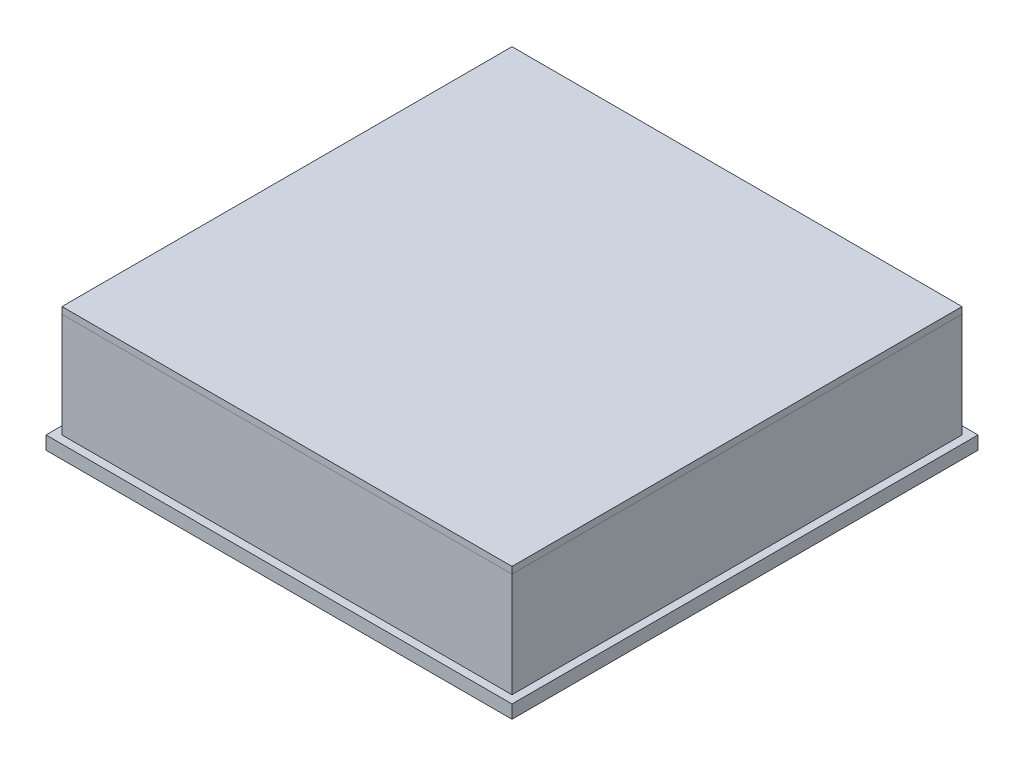
SolidWorks part; units mm, degrees
ref_plane "Front Plane" through (0, 0, 0) normal (0, 0, 1) x (1, 0, 0)
ref_plane "Top Plane" through (0, 0, 0) normal (0, 1, 0) x (1, 0, 0)
ref_plane "Right Plane" through (0, 0, 0) normal (1, 0, 0) x (0, 0, -1)
sketch "Sketch2" plane through (0, 0, 0) normal (0, 1, 0) x (1, 0, 0)
  line L0 (-4304.792, -4304.792) -> (-4304.792, 4304.792)
  line L1 (3999.992, -3999.992) -> (-3999.992, -3999.992)
  line L2 (3999.992, -3999.992) -> (3999.992, 3999.992)
  line L3 (3999.992, 3999.992) -> (-3999.992, 3999.992)
  line L4 (-3999.992, -3999.992) -> (-3999.992, 3999.992)
  line L5 (3999.992, -3999.992) -> (-3999.992, 3999.992) construction
  line L6 (3999.992, 3999.992) -> (-3999.992, -3999.992) construction
  line L7 (4304.792, 4304.792) -> (-4304.792, 4304.792)
  line L8 (4304.792, -4304.792) -> (4304.792, 4304.792)
  line L9 (4304.792, -4304.792) -> (-4304.792, -4304.792)
  point P0 (0, 0)
  dimension "D1" = 7999.984
  dimension "D2" = 7999.984
  dimension "D3" = 304.8
extrude "Boss-Extrude1" add sketch "Sketch2" along normal blind 1999.996
sketch "Sketch3" plane through (0, 0, 0) normal (0, -1, 0) x (1, 0, 0)
  line L0 (-4304.792, -4304.792) -> (-4304.792, 4304.792) construction
  line L1 (-4304.792, -4304.792) -> (-4304.792, 4304.792)
  line L2 (4304.792, -4304.792) -> (-4304.792, -4304.792) construction
  line L3 (4304.792, 4304.792) -> (4304.792, -4304.792) construction
  line L4 (-4304.792, 4304.792) -> (4304.792, 4304.792) construction
  line L5 (4304.792, -4304.792) -> (-4304.792, -4304.792)
  line L6 (4304.792, 4304.792) -> (4304.792, -4304.792)
  line L7 (-4304.792, 4304.792) -> (4304.792, 4304.792)
extrude "Boss-Extrude2" add sketch "Sketch3" along normal blind 152.4
sketch "Sketch6" plane through (0, 0, 0) normal (0, 1, 0) x (1, 0, 0)
  line L0 (0, 0) -> (-3999.992, 3999.992) construction
  line L6 (-3999.992, 1656.8509) -> (-1656.8509, 1656.8509) construction
  line L7 (-3999.992, 3999.992) -> (-3999.992, -3999.992) construction
  line L19 (-1656.8509, 1656.8509) -> (-1656.8509, 3999.992) construction
  line L20 (3999.992, 3999.992) -> (-3999.992, 3999.992) construction
  line L22 (-1656.8509, 1656.8509) -> (0, 0) construction
  line L24 (1809.2509, 1504.4509) -> (1809.2509, 1809.2509)
  line L25 (-1504.4509, 1809.2509) -> (-1809.2509, 1809.2509)
  line L29 (-1504.4509, 1809.2509) -> (-1504.4509, 1504.4509)
  line L30 (-1504.4509, 1504.4509) -> (-1809.2509, 1504.4509)
  line L31 (-1809.2509, 1809.2509) -> (-1809.2509, 1504.4509)
  line L32 (-1504.4509, 1809.2509) -> (-1809.2509, 1504.4509) construction
  line L33 (-1504.4509, 1504.4509) -> (-1809.2509, 1809.2509) construction
  line L34 (1809.2509, 1809.2509) -> (1504.4509, 1809.2509)
  line L35 (1504.4509, 1504.4509) -> (1504.4509, 1809.2509)
  line L36 (1809.2509, 1504.4509) -> (1504.4509, 1504.4509)
  line L37 (1504.4509, -1809.2509) -> (1809.2509, -1809.2509)
  line L38 (1809.2509, -1809.2509) -> (1809.2509, -1504.4509)
  line L39 (1504.4509, -1504.4509) -> (1809.2509, -1504.4509)
  line L40 (1504.4509, -1809.2509) -> (1504.4509, -1504.4509)
  line L41 (-1809.2509, -1504.4509) -> (-1809.2509, -1809.2509)
  line L42 (-1809.2509, -1809.2509) -> (-1504.4509, -1809.2509)
  line L43 (-1504.4509, -1504.4509) -> (-1504.4509, -1809.2509)
  line L44 (-1809.2509, -1504.4509) -> (-1504.4509, -1504.4509)
  point P30 (0, 0)
  dimension "D1" = 304.8
extrude "Boss-Extrude5" add sketch "Sketch6" along normal up to surface (1999.996 mm away) contours L25 L31 L30 L29 | L36 L24 L34 L35 | L40 L37 L38 L39 | L44 L41 L42 L43 region at (1656.8509, 0, -1656.8509) region at (-1656.8509, 0, -1656.8509) region at (1656.8509, 0, 1656.8509) region at (-1656.8509, 0, 1656.8509) up to face at (0, 1999.996, 0)
sketch "Sketch7" plane through (0, 1999.996, 0) normal (0, 1, 0) x (1, 0, 0)
  line L1 (4304.792, -4304.792) -> (-4304.792, -4304.792)
  line L2 (4304.792, -4304.792) -> (4304.792, 4304.792)
  line L3 (4304.792, 4304.792) -> (-4304.792, 4304.792)
  line L4 (-4304.792, -4304.792) -> (-4304.792, 4304.792)
  line L5 (4304.792, -4304.792) -> (-4304.792, 4304.792) construction
  line L6 (4304.792, 4304.792) -> (-4304.792, -4304.792) construction
  point P0 (0, 0)
extrude "Boss-Extrude6" add sketch "Sketch7" along normal blind 127 separate body
sketch "Sketch4" plane through (0, -152.4, 0) normal (0, -1, 0) x (1, 0, 0)
  line L30 (-4457.192, 4457.192) -> (-4457.192, -4457.192)
  line L31 (-4457.192, -4457.192) -> (4457.192, -4457.192)
  line L32 (4457.192, -4457.192) -> (4457.192, 4457.192)
  line L33 (4457.192, 4457.192) -> (-4457.192, 4457.192)
  line L34 (-4457.192, 4457.192) -> (-4457.192, -4457.192)
  line L35 (-4457.192, -4457.192) -> (4457.192, -4457.192)
  line L36 (4457.192, -4457.192) -> (4457.192, 4457.192)
  line L37 (4457.192, 4457.192) -> (-4457.192, 4457.192)
  line L43 (3847.592, 3847.592) -> (-3847.592, 3847.592)
  line L44 (-3847.592, 3847.592) -> (-3847.592, -3847.592)
  line L45 (-3847.592, -3847.592) -> (3847.592, -3847.592)
  line L46 (3847.592, -3847.592) -> (3847.592, 3847.592)
  line L47 (3847.592, 3847.592) -> (-3847.592, 3847.592)
  line L48 (-3847.592, 3847.592) -> (-3847.592, -3847.592)
  line L49 (-3847.592, -3847.592) -> (3847.592, -3847.592)
  line L50 (3847.592, -3847.592) -> (3847.592, 3847.592)
  dimension "D1" = 152.4
  dimension "D2" = 152.4
extrude "Boss-Extrude3" [suppressed] add sketch "Sketch4" along normal blind 304.8
sketch "Sketch8" plane through (0, 0, -1504.4509) normal (0, 0, 1) x (1, 0, 0)
  line L0 (-3999.992, 1999.996) -> (-3999.992, 0) construction
  line L1 (3999.992, 1999.996) -> (-3999.992, 1999.996)
  line L2 (3999.992, 1999.996) -> (3999.992, 1753.1524)
  line L3 (3999.992, 1753.1524) -> (-3999.992, 1753.1524)
  line L4 (-3999.992, 1999.996) -> (-3999.992, 1753.1524)
  line L5 (3999.992, 1999.996) -> (-3999.992, 1753.1524) construction
  line L6 (3999.992, 1753.1524) -> (-3999.992, 1999.996) construction
  line L7 (3999.992, 1999.996) -> (-3999.992, 1999.996) construction
  line L8 (3999.992, 1999.996) -> (-3999.992, 1999.996)
  point P0 (0, 1876.5742)
ref_axis "Axis1" through (0, 0, 0) along (0, 1, 0)
sketch "Right Plane Rebar" [suppressed] plane through (0, 0, 0) normal (1, 0, 0) x (0, 0, -1)
  line L0 (4234.942, 2063.496) -> (4234.942, -393.7)
  line L1 (-4457.192, -457.2) -> (4457.192, -457.2) construction
  line L2 (4069.842, 2044.446) -> (4069.842, 50.8)
  line L3 (4222.242, 1314.196) -> (4222.242, 1923.796)
  line L4 (-4304.792, 1999.996) -> (-4304.792, -152.4)
  line L5 (-4304.792, -152.4) -> (4304.792, -152.4)
  line L6 (4304.792, -152.4) -> (4304.792, 1999.996)
  line L7 (4304.792, 1999.996) -> (-4304.792, 1999.996)
  line L8 (-4304.792, 1999.996) -> (-4304.792, -152.4)
  line L10 (4304.792, -152.4) -> (4304.792, 1999.996)
  line L12 (4095.242, 2050.796) -> (3485.642, 2050.796)
  line L13 (4095.242, 2063.496) -> (-4095.242, 2063.496)
  line L14 (0, 1421.3078) -> (0, -1421.3078) construction
  line L15 (3955.542, -88.9) -> (-3955.542, -88.9)
  line L16 (3999.992, 1999.996) -> (-3999.992, 1999.996)
  line L17 (3999.992, 1999.996) -> (-3999.992, 1999.996)
  line L18 (-4304.792, 2126.996) -> (4304.792, 2126.996) construction
  line L19 (3999.992, 0) -> (3999.992, 1999.996)
  line L20 (-3999.992, 0) -> (3999.992, 0)
  line L21 (-3999.992, 1999.996) -> (-3999.992, 0)
  line L27 (3999.992, 0) -> (3999.992, 1999.996)
  line L28 (-3999.992, 0) -> (3999.992, 0)
  line L29 (-3999.992, 1999.996) -> (-3999.992, 0)
  line L32 (4082.542, 660.4) -> (4082.542, 50.8)
  line L33 (3955.542, -76.2) -> (3345.942, -76.2)
  line L37 (-4304.792, -152.4) -> (4304.792, -152.4)
  line L38 (4304.792, 1999.996) -> (-4304.792, 1999.996)
  arc A0 (4222.242, 1923.796) -> (4095.242, 2050.796) centre (4095.242, 1923.796) ccw
  arc A1 (3955.542, -76.2) -> (4082.542, 50.8) centre (3955.542, 50.8) ccw
  point P23 (4222.242, 2050.796)
  point P30 (0, 2063.496)
  point P41 (0, -88.9)
  dimension "D12" = 127
  dimension "D19" = 127
  dimension "D5" = 69.85
  dimension "Vertical Rebar Outer" = 2457.196
  dimension "D4" = 63.5
  dimension "D8" = 69.85
  dimension "D11" = 12.7
  dimension "D10" = 6.35
  dimension "D13" = 24000
  dimension "D14" = 609.6
  dimension "D15" = 12.7
  dimension "D17" = 12.7
  dimension "D18" = 12.7
  dimension "D7" = 609.6
  dimension "D20" = 609.6
  dimension "Vertical Rebar Inner" = 1993.646
  dimension "Lid Rebar Length" = 8190.484
  dimension "Base Rebar Length" = 7911.084
  dimension "D3" = 63.5
  dimension "D6" = 63.5
  dimension "D1" = 0
  dimension "D2" = 0
sketch "Front Plane Rebar" [suppressed] plane through (0, 0, 0) normal (0, 0, 1) x (1, 0, 0)
  line L0 (4247.642, 2063.496) -> (4247.642, -393.7)
  line L1 (3999.992, 1999.996) -> (3999.992, 0) construction
  line L2 (4057.142, 2031.746) -> (4057.142, 63.5)
  line L3 (4234.942, 1301.496) -> (4234.942, 1911.096)
  line L4 (-4304.792, 2126.996) -> (4304.792, 2126.996) construction
  line L5 (4457.192, -457.2) -> (-4457.192, -457.2) construction
  line L6 (4457.192, -152.4) -> (-4457.192, -152.4) construction
  line L7 (4304.792, 2126.996) -> (-4304.792, 2126.996) construction
  line L8 (-4304.792, 1999.996) -> (-4304.792, -152.4)
  line L9 (-4304.792, -152.4) -> (4304.792, -152.4)
  line L10 (4304.792, -152.4) -> (4304.792, 1999.996)
  line L12 (4107.942, 2038.096) -> (3498.342, 2038.096)
  line L13 (4107.942, 2050.796) -> (-4107.942, 2050.796)
  line L15 (3942.842, -76.2) -> (-3942.842, -76.2)
  line L17 (3999.992, 1999.996) -> (-3999.992, 1999.996)
  line L19 (-3999.992, 0) -> (3999.992, 0)
  line L20 (3999.992, 0) -> (3999.992, 1999.996)
  line L21 (3999.992, 1999.996) -> (-3999.992, 1999.996)
  line L22 (-3999.992, 1999.996) -> (-3999.992, 0)
  line L23 (-3999.992, 0) -> (3999.992, 0)
  line L27 (3999.992, 0) -> (3999.992, 1999.996)
  line L28 (-3999.992, 0) -> (3999.992, 0)
  line L29 (-3999.992, 1999.996) -> (-3999.992, 0)
  line L32 (4069.842, 673.1) -> (4069.842, 63.5)
  line L33 (3942.842, -63.5) -> (3333.242, -63.5)
  line L34 (3999.992, 0) -> (3999.992, 1999.996)
  line L35 (3999.992, 1999.996) -> (-3999.992, 1999.996)
  line L36 (-3999.992, 1999.996) -> (-3999.992, 0)
  line L37 (4304.792, -152.4) -> (4304.792, 1999.996)
  line L38 (4304.792, 1999.996) -> (-4304.792, 1999.996)
  line L39 (-4304.792, -152.4) -> (4304.792, -152.4)
  line L40 (-4304.792, 1999.996) -> (-4304.792, -152.4)
  line L41 (4304.792, 1999.996) -> (-4304.792, 1999.996)
  line L42 (4304.792, -152.4) -> (4304.792, 1999.996)
  line L44 (-4304.792, 1999.996) -> (-4304.792, -152.4)
  line L45 (4304.792, 1999.996) -> (-4304.792, 1999.996)
  line L48 (-4304.792, -152.4) -> (4304.792, -152.4)
  arc A0 (4234.942, 1911.096) -> (4107.942, 2038.096) centre (4107.942, 1911.096) ccw
  arc A1 (3942.842, -63.5) -> (4069.842, 63.5) centre (3942.842, 63.5) ccw
  point P23 (4234.942, 2038.096)
  point P30 (0, 2050.796)
  point P41 (0, -76.2)
  dimension "D13" = 609.6
  dimension "D12" = 127
  dimension "D19" = 127
  dimension "D3" = 76.2
  dimension "D4" = 63.5
  dimension "D5" = 57.15
  dimension "D6" = 0
  dimension "D7" = 609.6
  dimension "D8" = 57.15
  dimension "Vertical Rebar Outer" = 2457.196
  dimension "D9" = 0
  dimension "D10" = 6.35
  dimension "D11" = 12.7
  dimension "D14" = 609.6
  dimension "D15" = 12.7
  dimension "D16" = 76.2
  dimension "D17" = 12.7
  dimension "D18" = 12.7
  dimension "D20" = 609.6
  dimension "D21" = 63.5
  dimension "Vertical Rebar Inner" = 1968.246
  dimension "Lid Rebar Length" = 8215.884
  dimension "Base Rebar Length" = 7885.684
sketch "Sketch9" [suppressed] plane through (0, -152.4, 0) normal (0, 1, 0) x (1, 0, 0)
  line L0 (-4260.342, 4393.692) -> (-4260.342, -4393.692)
  line L1 (-4457.192, -4457.192) -> (-4457.192, 4457.192) construction
  line L2 (-4457.192, -4457.192) -> (-4457.192, 4457.192)
  line L3 (-3847.592, -3847.592) -> (-3847.592, 3847.592) construction
  line L4 (-3847.592, -3847.592) -> (-3847.592, 3847.592)
  line L5 (-4457.192, 4457.192) -> (4457.192, 4457.192) construction
  line L6 (4457.192, -4457.192) -> (-4457.192, -4457.192) construction
  line L7 (-4044.442, 4152.392) -> (-4044.442, -4152.392)
  line L8 (4393.692, 4260.342) -> (-4393.692, 4260.342)
  line L9 (4152.392, 4044.442) -> (-4152.392, 4044.442)
  line L10 (4260.342, -4393.692) -> (4260.342, 4393.692)
  line L11 (4044.442, -4152.392) -> (4044.442, 4152.392)
  line L12 (-4393.692, -4260.342) -> (4393.692, -4260.342)
  line L13 (-4152.392, -4044.442) -> (4152.392, -4044.442)
  point P27 (0, 0)
  dimension "D1" = 196.85
  dimension "D2" = 63.5
  dimension "D3" = 63.5
  dimension "D4" = 196.85
  dimension "D5" = 304.8
  dimension "D6" = 304.8
  dimension "D7" = 8787.384
  dimension "D8" = 8304.784
  dimension "D9" = 4
sketch "Sketch11" [suppressed] plane through (0, 0, -1504.4509) normal (0, 0, 1) x (1, 0, 0)
  line L0 (-1745.7509, 2063.496) -> (-1745.7509, -88.9)
  line L1 (-1745.7509, 2063.496) -> (-1745.7509, 1930.146)
  line L2 (-4304.792, 2126.996) -> (4304.792, 2126.996) construction
  line L4 (4457.192, -152.4) -> (-4457.192, -152.4) construction
  line L5 (-1745.7509, -88.9) -> (-1745.7509, 44.45)
  line L6 (-1504.4509, 0) -> (-1504.4509, 1999.996)
  line L7 (-1504.4509, 1999.996) -> (-1809.2509, 1999.996)
  line L8 (-1809.2509, 1999.996) -> (-1809.2509, 0)
  line L9 (-1809.2509, 0) -> (-1504.4509, 0)
  line L10 (-1504.4509, 0) -> (-1504.4509, 1999.996)
  line L11 (-1504.4509, 1999.996) -> (-1809.2509, 1999.996)
  line L12 (-1809.2509, 1999.996) -> (-1809.2509, 0)
  line L13 (-1809.2509, 0) -> (-1504.4509, 0)
  dimension "D2" = 63.5
  dimension "D3" = 133.35
  dimension "D4" = 63.5
  dimension "D5" = 63.5
  dimension "D6" = 133.35
  dimension "D7" = 1885.696
  dimension "D1" = 0
sketch "Sketch13" [suppressed] plane through (0, 2126.996, 0) normal (0, 1, 0) x (1, 0, 0)
  line L0 (-4222.242, 4253.992) -> (-4222.242, -4253.992)
  line L1 (-4304.792, 4304.792) -> (-4304.792, -4304.792) construction
  line L2 (-4304.792, 4304.792) -> (4304.792, 4304.792) construction
  line L3 (4304.792, -4304.792) -> (-4304.792, -4304.792) construction
  dimension "D1" = 82.55
  dimension "D2" = 50.8
  dimension "D3" = 50.8
  dimension "D4" = 8507.984
ref_plane "Plane1" through (-4304.792, 1999.996, -4304.792) normal (0, -1, 0) x (-1, 0, 0)
sketch "Sketch14" plane through (0, 0, 0) normal (0, 1, 0) x (1, 0, 0)
  line L0 (-4304.792, 4304.792) -> (-4304.792, -4304.792) construction
  line L1 (4457.192, -4457.192) -> (-4457.192, -4457.192)
  line L2 (4457.192, -4457.192) -> (4457.192, 4457.192)
  line L3 (4457.192, 4457.192) -> (-4457.192, 4457.192)
  line L4 (-4457.192, -4457.192) -> (-4457.192, 4457.192)
  line L5 (4457.192, -4457.192) -> (-4457.192, 4457.192) construction
  line L6 (4457.192, 4457.192) -> (-4457.192, -4457.192) construction
  line L7 (4304.792, 4304.792) -> (-4304.792, 4304.792) construction
  point P0 (0, 0)
  dimension "D1" = 152.4
  dimension "D2" = 152.4
extrude "Boss-Extrude7" add sketch "Sketch14" against normal blind 254
sketch "Sketch15" plane through (0, 2126.996, 0) normal (0, 1, 0) x (1, 0, 0)
  line L0 (4304.792, -4304.792) -> (4304.792, 4304.792) construction
  line L1 (-3999.992, -3999.992) -> (3999.992, -3999.992)
  line L2 (-3999.992, -3999.992) -> (-3999.992, 3999.992)
  line L3 (-3999.992, 3999.992) -> (3999.992, 3999.992)
  line L4 (3999.992, -3999.992) -> (3999.992, 3999.992)
  line L5 (-3999.992, -3999.992) -> (3999.992, 3999.992) construction
  line L6 (-3999.992, 3999.992) -> (3999.992, -3999.992) construction
  line L7 (4304.792, 4304.792) -> (-4304.792, 4304.792) construction
  line L9 (3085.592, 3491.992) -> (3999.992, 3491.992)
  line L10 (3085.592, 3491.992) -> (3085.592, 2577.592)
  line L11 (3085.592, 2577.592) -> (3999.992, 2577.592)
  line L12 (3999.992, 3491.992) -> (3999.992, 2577.592)
  line L13 (3085.592, 3491.992) -> (3999.992, 2577.592) construction
  line L14 (3085.592, 2577.592) -> (3999.992, 3491.992) construction
  point P0 (0, 0)
  point P10 (3542.792, 3034.792)
  dimension "D1" = 304.8
  dimension "D2" = 304.8
  dimension "D3" = 914.4
  dimension "D4" = 914.4
  dimension "D5" = 965.2
sketch "Sketch17" plane through (0, 0, 0) normal (0, 0, 1) x (1, 0, 0)
  line L0 (-4000, -254) -> (-4000, -150)
  line L1 (4457.192, -254) -> (-4457.192, -254) construction
  line L2 (-4000, -150) -> (4000, -150)
  line L3 (4000, -150) -> (4000, -254)
  line L4 (4000, -254) -> (-4000, -254)
  line L5 (3999.992, 0) -> (-3999.992, 0) construction
  point P5 (0, -150)
  point P8 (3958.1256, -254)
  point P13 (-3625.414, -127.765)
  dimension "D1" = 150
  dimension "D3" = 8000
extrude "Cut-Extrude1" cut sketch "Sketch17" against normal blind 4000 and the other way blind 4000 contours L4 L3 L2 L0 region at (0, -202, 0)
sketch "Sketch18" plane through (0, 0, 0) normal (1, 0, 0) x (0, 0, -1)
  line L0 (0, -254) -> (4000, -254)
  line L1 (-4000, -254) -> (4000, -254) construction
  line L2 (4457.192, -254) -> (-4457.192, -254) construction
  line L3 (4000, -254) -> (4000, -150) construction
  line L4 (4000, -254) -> (3410.1867, -150)
  line L5 (-4000, -150) -> (4000, -150) construction
  line L6 (3410.1867, -150) -> (4000, -150)
  line L7 (4000, -150) -> (4000, -254)
  dimension "D1" = 10
extrude "Boss-Extrude9" add sketch "Sketch18" along normal blind 4000 and the other way blind 4000 contours L7 L6 L4 region at (0, -184.6667, -3803.3956)
pattern_circular "CirPattern3" count 4 over 360 about axis through (0, 0, 0) along (0, 1, 0) of "Boss-Extrude9"
equation "\"Contact Length\"= 24"
equation "\"Rebar Bend Radius\"= 5"
equation "\"D13@Right Plane Rebar\" = \"Contact Length\""
